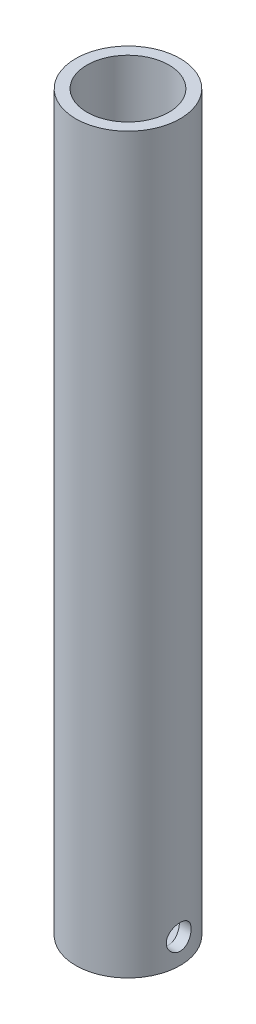
SolidWorks part; units mm, degrees
material "6063-T5"
ref_plane "Front Plane" through (0, 0, 0) normal (0, 0, 1) x (1, 0, 0)
ref_plane "Top Plane" through (0, 0, 0) normal (0, 1, 0) x (1, 0, 0)
ref_plane "Right Plane" through (0, 0, 0) normal (1, 0, 0) x (0, 0, -1)
sketch "Sketch1" plane through (0, 0, 0) normal (0, 1, 0) x (1, 0, 0)
  circle A0 centre (0, 0) radius 10.4648
  circle A1 centre (0, 0) radius 13.335
  dimension "D1" = 20.9296
  dimension "D2" = 26.67
extrude "Boss-Extrude1" add sketch "Sketch1" along normal blind 187.325
extrude "Boss-Extrude2" add sketch "Sketch1<2>" along normal blind 3.175 contours A0
sketch "Sketch1<2>" plane through (0, 0, 0) normal (0, 1, 0) x (1, 0, 0) same geometry as "Sketch1"
ref_plane "Plane1" through (13.335, 0, 0) normal (1, 0, 0) x (0, 0, -1)
sketch "Sketch3" plane through (13.335, 0, 0) normal (1, 0, 0) x (0, 0, -1)
  line L0 (0, -187.325) -> (0, 187.325) construction
  line L1 (13.335, 187.325) -> (-13.335, 187.325) construction
  line L2 (-13.335, 0) -> (13.335, 0) construction
  circle A0 centre (0, 6.35) radius 3.175
  point P0 (0, 6.35)
  point P6 (0, 0)
  dimension "D2" = 6.35
  dimension "D1" = 6.35
extrude "Cut-Extrude1" cut sketch "Sketch3" against normal blind 14.351
